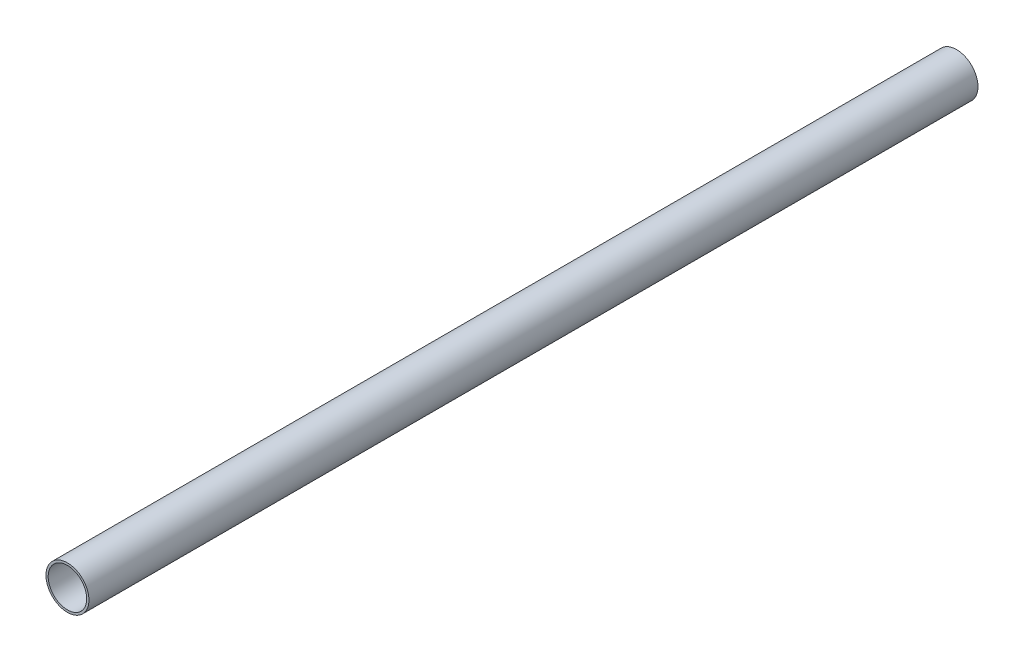
SolidWorks part; units mm, degrees
material "Copper"
ref_plane "Front" through (0, 0, 0) normal (0, 0, 1) x (1, 0, 0)
ref_plane "Top" through (0, 0, 0) normal (0, 1, 0) x (1, 0, 0)
ref_plane "Right" through (0, 0, 0) normal (1, 0, 0) x (0, 0, -1)
sketch "Sketch1" plane through (0, 0, 0) normal (0, 0, 1) x (1, 0, 0)
  circle A0 centre (0, 0) radius 11.1125
  circle A1 centre (0, 0) radius 9.9695
  dimension "D1" = 22.225
  dimension "D2" = 19.939
extrude "Boss-Extrude1" add sketch "Sketch1" along normal mid plane 460
